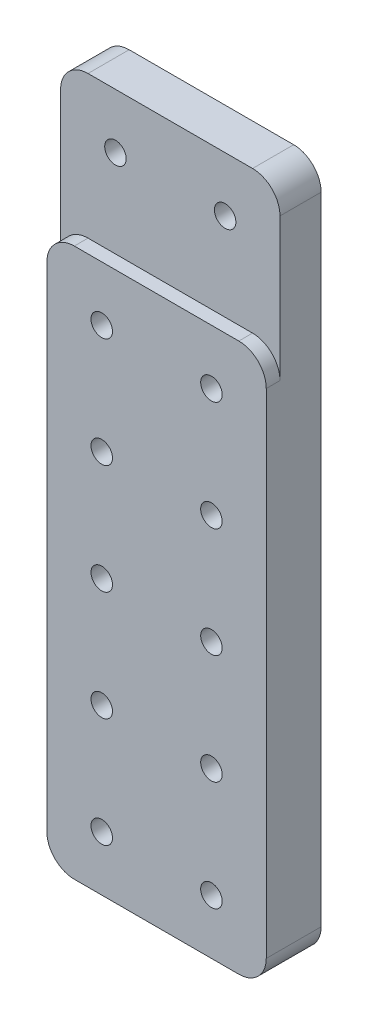
SolidWorks part; units mm, degrees
material "PET"
ref_plane "Front Plane" through (0, 0, 0) normal (0, 0, 1) x (1, 0, 0)
ref_plane "Top Plane" through (0, 0, 0) normal (0, 1, 0) x (1, 0, 0)
ref_plane "Right Plane" through (0, 0, 0) normal (1, 0, 0) x (0, 0, -1)
sketch "Sketch2" plane through (0, 0, 0) normal (0, 0, 1) x (1, 0, 0)
  line L1 (0, 0) -> (50.8, 0)
  line L2 (0, 0) -> (0, 160.02)
  line L3 (0, 160.02) -> (50.8, 160.02)
  line L4 (50.8, 0) -> (50.8, 160.02)
  dimension "D1" = 50.8
  dimension "D2" = 160.02
extrude "Boss-Extrude1" add sketch "Sketch2" against normal blind 12.7
sketch "Sketch3" plane through (0, 0, 0) normal (0, 0, 1) x (1, 0, 0)
  line L0 (50.8, 160.02) -> (0, 160.02) construction
  line L1 (0, 160.02) -> (0, 0) construction
  circle A0 centre (12.7, 147.32) radius 2.4892
  circle A17 centre (38.1, 147.32) radius 2.4892
  circle A24 centre (12.7, 114.3) radius 2.4892
  circle A25 centre (12.7, 88.9) radius 2.4892
  circle A26 centre (12.7, 63.5) radius 2.4892
  circle A27 centre (12.7, 38.1) radius 2.4892
  circle A28 centre (12.7, 12.7) radius 2.4892
  circle A29 centre (38.1, 88.9) radius 2.4892
  circle A30 centre (38.1, 63.5) radius 2.4892
  circle A31 centre (38.1, 38.1) radius 2.4892
  circle A32 centre (38.1, 12.7) radius 2.4892
  circle A33 centre (38.1, 114.3) radius 2.4892
  dimension "D1" = 4.9784
  dimension "D6" = 4.9784
  dimension "D2" = 12.7
  dimension "D3" = 12.7
  dimension "D7" = 12.7
  dimension "D8" = 33.02
  dimension "D4" = 1
  dimension "D5" = 2
  dimension "D9" = 5
  dimension "D10" = 2
extrude "Cut-Extrude1" cut sketch "Sketch3" against normal through all
fillet "Fillet1" radius 6.35 4 edges at (0, 0, -6.35) (50.8, 0, -6.35) (50.8, 160.02, -6.35) (0, 160.02, -6.35)
sketch "Sketch4" plane through (0, 0, 0) normal (-1, 0, 0) x (0, 0, 1)
  line L1 (-3.175, 160.02) -> (0, 160.02)
  line L2 (-3.175, 160.02) -> (-3.175, 127)
  line L3 (-3.175, 127) -> (0, 127)
  line L4 (0, 160.02) -> (0, 127)
  line L5 (0, 153.67) -> (0, 6.35) construction
  line L6 (-12.7, 160.02) -> (0, 160.02) construction
  dimension "D1" = 33.02
  dimension "D2" = 3.175
extrude "Cut-Extrude2" cut sketch "Sketch4" against normal through all
fillet "Fillet3" radius 6.35 2 edges at (50.8, 127, -1.5875) (0, 127, -1.5875)
